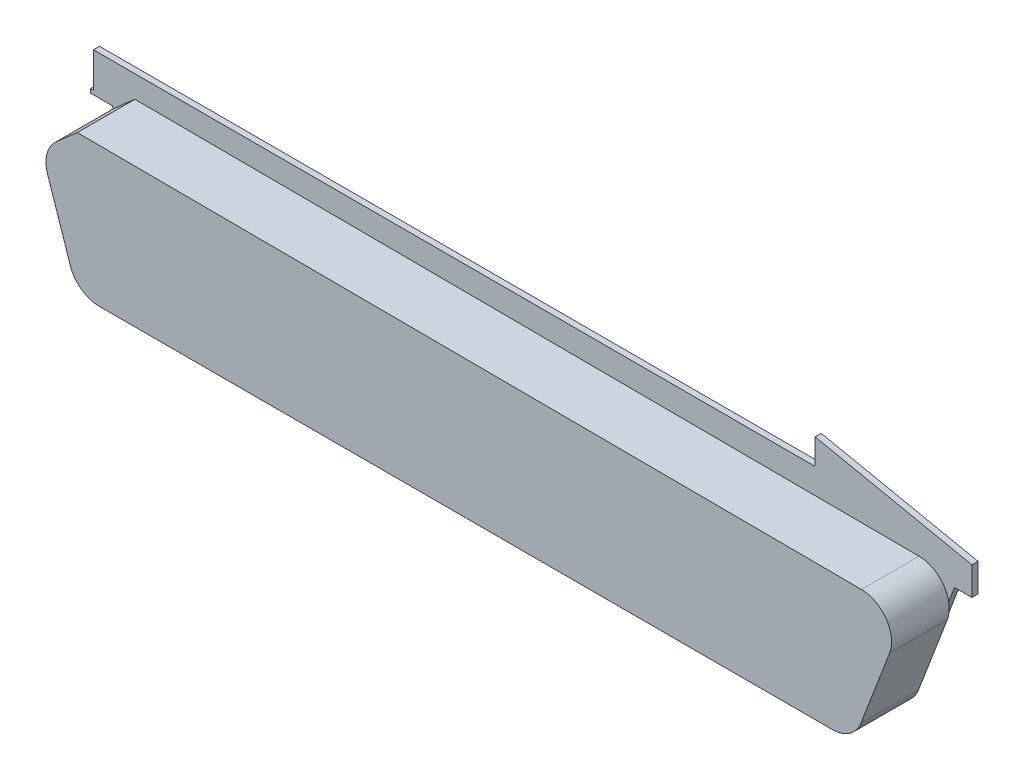
SolidWorks part; units mm, degrees
ref_plane "Front Plane" through (0, 0, 0) normal (0, 0, 1) x (1, 0, 0)
ref_plane "Top Plane" through (0, 0, 0) normal (0, 1, 0) x (1, 0, 0)
ref_plane "Right Plane" through (0, 0, 0) normal (1, 0, 0) x (0, 0, -1)
sketch "Sketch1" plane through (0, 0, 0) normal (0, 0, 1) x (1, 0, 0)
  line L0 (-736.6487, 88.883) -> (453.4188, 88.883)
  line L1 (453.4188, 88.883) -> (453.4188, 173.4825)
  line L2 (453.4188, 173.4825) -> (711.9535, 124.4672)
  line L3 (711.9535, 124.4672) -> (711.9535, 30.9935)
  line L4 (711.9535, 30.9935) -> (683.209, 30.9935)
  line L5 (683.209, 30.9935) -> (659.264, -32.0025)
  line L6 (659.264, -32.0025) -> (641.9526, -32.0025)
  line L7 (641.9526, -32.0025) -> (632.6344, -56.5174)
  line L8 (632.6344, -56.5174) -> (353.5907, -101.1644)
  line L9 (353.5907, -101.1644) -> (-642.9779, -101.1644)
  line L10 (-642.9779, -101.1644) -> (-674.8533, -32.0025)
  line L11 (-674.8533, -32.0025) -> (-679.2636, -32.0025)
  line L12 (-679.2636, -32.0025) -> (-705.3324, 24.5605)
  line L13 (-705.3324, 24.5605) -> (-741.6487, 24.5605)
  line L14 (-741.6487, 24.5605) -> (-741.6487, 30.9935)
  line L15 (-741.6487, 30.9935) -> (-736.6487, 30.9935)
  line L16 (-736.6487, 30.9935) -> (-736.6487, 88.883)
extrude "Boss-Extrude1" add sketch "Sketch1" along normal blind 10
sketch "Sketch3" plane through (0, 0, 10) normal (0, 0, 1) x (1, 0, 0)
  line L1 (671.1675, -21.4674) -> (623.6367, -145.511)
  line L4 (576.947, -177.6205) -> (-632.2431, -177.6205)
  line L5 (-679.6468, -143.5231) -> (-717.2215, -31.5172)
  line L6 (-702.823, 21.9441) -> (-668.2081, 52.3624)
  line L7 (-668.2081, 52.3624) -> (624.7074, 46.4225)
  arc A6 (-632.2431, -177.6205) -> (-679.6468, -143.5231) centre (-632.2431, -127.6205) cw
  arc A7 (623.6367, -145.511) -> (576.947, -177.6205) centre (576.947, -127.6205) cw
  arc A8 (671.1675, -21.4674) -> (624.7074, 46.4225) centre (624.4777, -3.577) ccw
  arc A9 (-717.2215, -31.5172) -> (-702.823, 21.9441) centre (-669.8178, -15.6146) cw
  point P5 (0, 0)
  dimension "D1" = 50
  dimension "D2" = 50
extrude "Boss-Extrude2" add sketch "Sketch3" along normal blind 95
sketch "Sketch4" plane through (0, 0, 10) normal (0, 0, 1) x (1, 0, 0)
  line L0 (453.4188, 131.1827) -> (711.9535, 77.7303)
  line L1 (453.4188, 173.4825) -> (453.4188, 88.883) construction
  line L2 (711.9535, 30.9935) -> (711.9535, 124.4672) construction
  line L3 (453.4188, 131.1827) -> (453.4188, 173.4825)
  line L4 (453.4188, 173.4825) -> (711.9535, 124.4672)
  line L5 (711.9535, 124.4672) -> (711.9535, 77.7303)
extrude "Cut-Extrude1" cut sketch "Sketch4" against normal blind 95
fillet "Fillet1" [suppressed] radius 20
ref_plane "Plane1" [suppressed] through (0, 0, 57.5) normal (0, 0, 1) x (1, 0, 0)
sketch "Sketch6" [suppressed] plane through (0, 0, 57.5) normal (0, 0, 1) x (1, 0, 0)
  line L0 (-649.2296, 52.2752) -> (624.7074, 46.4225)
  line L1 (671.1675, -21.4674) -> (623.6367, -145.511)
  line L2 (576.947, -177.6205) -> (-632.2431, -177.6205)
  line L3 (-679.6468, -143.5231) -> (-717.2215, -31.5172)
  line L4 (-682.4645, 39.8344) -> (-702.823, 21.9441)
  arc A0 (-649.2296, 52.2752) -> (-682.4645, 39.8344) centre (-649.4593, 2.2757) ccw
  arc A1 (-702.823, 21.9441) -> (-717.2215, -31.5172) centre (-669.8178, -15.6146) ccw
  arc A2 (-679.6468, -143.5231) -> (-632.2431, -177.6205) centre (-632.2431, -127.6205) ccw
  arc A3 (671.1675, -21.4674) -> (624.7074, 46.4225) centre (624.4777, -3.577) ccw
  arc A4 (576.947, -177.6205) -> (623.6367, -145.511) centre (576.947, -127.6205) ccw
  point P20 (-668.2081, 52.3624)
  dimension "D1" = 50
